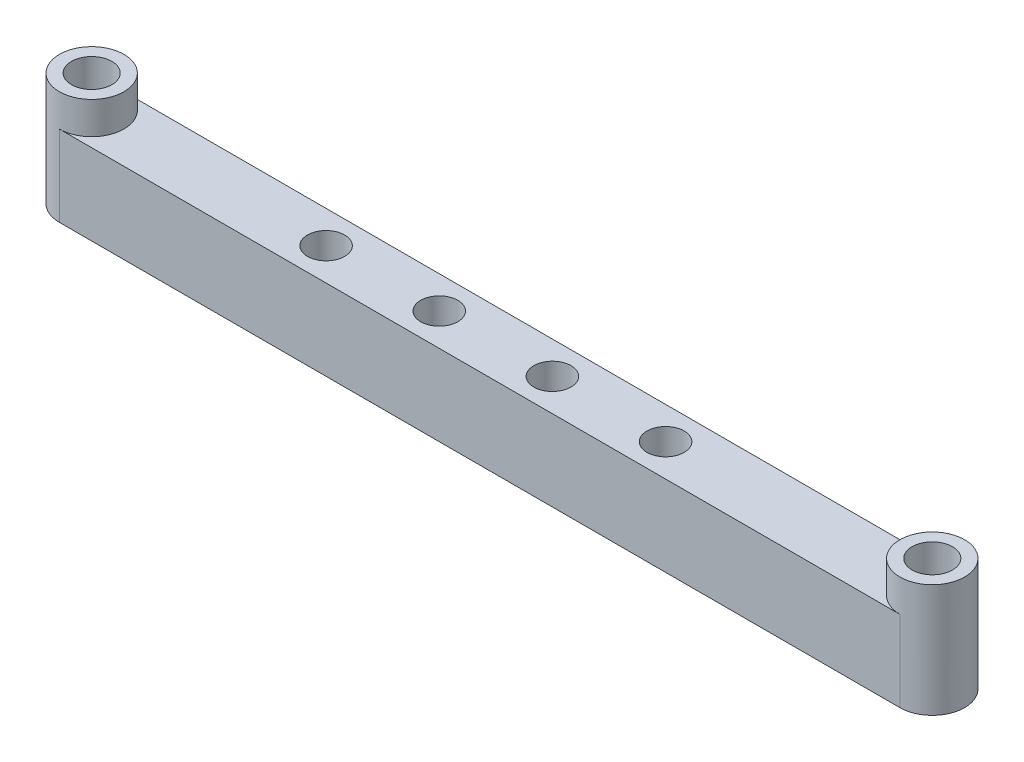
SolidWorks part; units mm, degrees
ref_plane "Front Plane" through (0, 0, 0) normal (0, 0, 1) x (1, 0, 0)
ref_plane "Top Plane" through (0, 0, 0) normal (0, 1, 0) x (1, 0, 0)
ref_plane "Right Plane" through (0, 0, 0) normal (1, 0, 0) x (0, 0, -1)
sketch "Sketch1" plane through (0, 0, 0) normal (0, 1, 0) x (1, 0, 0)
  line L1 (0, 0) -> (56, 0)
  line L2 (0, 0) -> (0, 4)
  line L3 (0, 4) -> (56, 4)
  line L4 (56, 0) -> (56, 4)
  line L5 (0, 2) -> (56, 2) construction
  circle A0 centre (2, 2) radius 1.25
  circle A1 centre (16.5, 2) radius 1.15
  circle A2 centre (23.5, 2) radius 1.15
  circle A3 centre (54, 2) radius 1.25
  circle A4 centre (30.5, 2) radius 1.15
  circle A5 centre (37.5, 2) radius 1.15
  point P5 (0, 0)
  point P6 (0, 0)
  point P21 (32.6488, 0.8747)
  dimension "D3" = 2.5
  dimension "D5" = 2.3
  dimension "D1" = 56
  dimension "D2" = 4
  dimension "D4" = 2
  dimension "D6" = 16.5
  dimension "D7" = 7
  dimension "D8" = 7
  dimension "D9" = 23.5
  dimension "D10" = 7
  dimension "D11" = 2
  dimension "D12" = 16.5
extrude "Boss-Extrude1" add sketch "Sketch1" along normal blind 5
fillet "Fillet1" radius 2 4 edges at (56, 2.5, -4) (56, 2.5, 0) (0, 2.5, -4) (0, 2.5, 0)
sketch "Sketch2" plane through (0, 5, 0) normal (0, 1, 0) x (1, 0, 0)
  circle A0 centre (2, 2) radius 1.25
  circle A1 centre (2, 2) radius 2
  circle A2 centre (54, 2) radius 1.25
  circle A3 centre (54, 2) radius 2
extrude "Boss-Extrude2" add sketch "Sketch2" along normal blind 2
